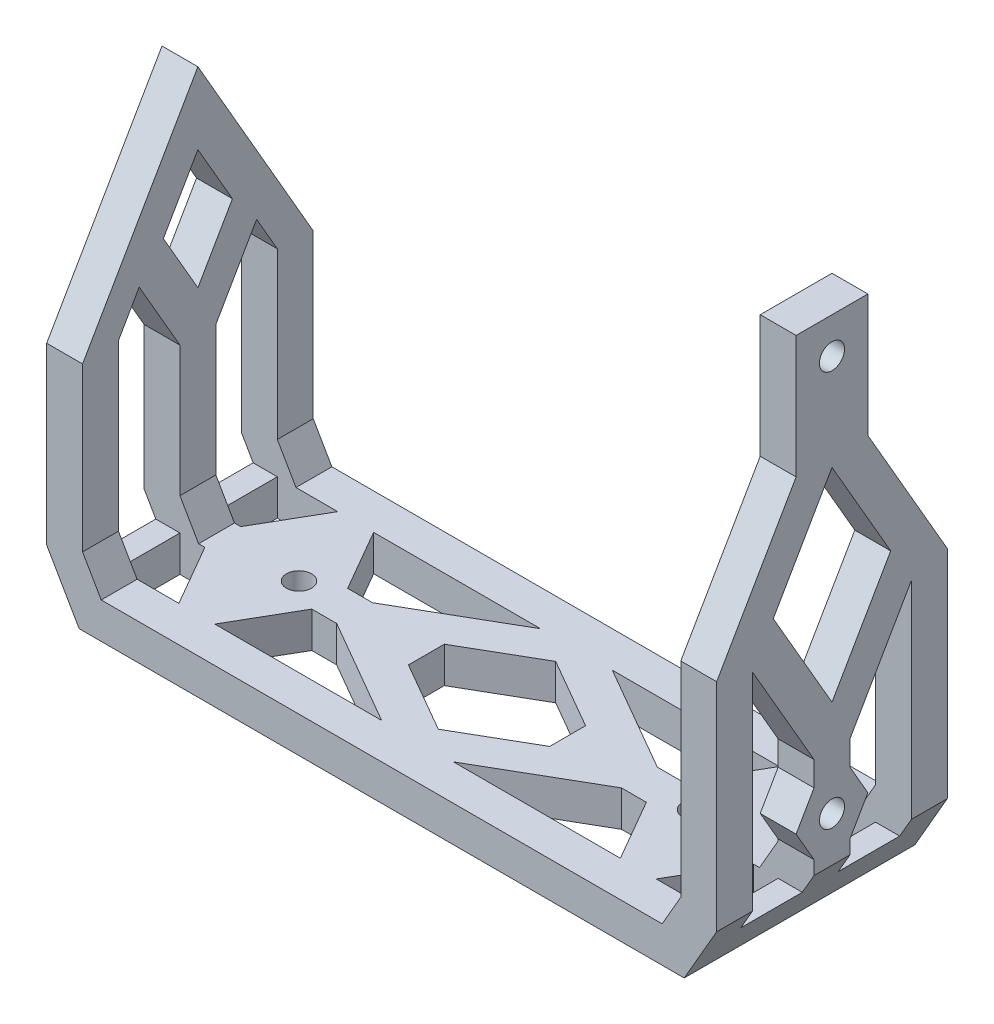
SolidWorks part; units mm, degrees
material "ABS"
ref_plane "Front Plane" through (0, 0, 0) normal (0, 0, 1) x (1, 0, 0)
ref_plane "Top Plane" through (0, 0, 0) normal (0, 1, 0) x (1, 0, 0)
ref_plane "Right Plane" through (0, 0, 0) normal (1, 0, 0) x (0, 0, -1)
sketch "Sketch1" plane through (0, 0, 0) normal (0, 1, 0) x (1, 0, 0)
  line L0 (-16.55, 0) -> (16.55, 0) construction
  line L1 (-5.9019, 1.5) -> (0, 4.9075)
  line L2 (-28, -1.5) -> (28, -1.5) construction
  line L3 (-28, -1.5) -> (-28, 1.5)
  line L4 (-28, 1.5) -> (28, 1.5) construction
  line L5 (28, -1.5) -> (28, 1.5)
  line L6 (-28, -1.5) -> (28, 1.5) construction
  line L7 (-28, 1.5) -> (28, -1.5) construction
  line L8 (0, 4.9075) -> (5.9019, 1.5)
  line L9 (-11.9019, 1.5) -> (-3, 6.6395)
  line L10 (11.9019, 1.5) -> (3, 6.6395)
  line L11 (0, 4.9075) -> (0, 6.6395) construction
  line L12 (-3, 6.6395) -> (3, 6.6395) construction
  line L13 (-28, 9.6395) -> (-28, 6.6395)
  line L14 (-28, 9.6395) -> (28, 9.6395)
  line L15 (-28, 6.6395) -> (28, 6.6395) construction
  line L16 (28, 9.6395) -> (28, 6.6395)
  line L17 (-28, 9.6395) -> (28, 6.6395) construction
  line L18 (-28, 6.6395) -> (28, 9.6395) construction
  line L19 (-11.9019, 1.5) -> (-5.9019, 1.5) construction
  line L20 (-5.9019, -1.5) -> (0, -4.9075)
  line L21 (5.9019, -1.5) -> (0, -4.9075)
  line L22 (-11.9019, -1.5) -> (-3, -6.6395)
  line L23 (11.9019, -1.5) -> (3, -6.6395)
  line L24 (0, -4.9075) -> (0, -6.6395) construction
  line L25 (-3, -6.6395) -> (3, -6.6395) construction
  line L26 (-28, -9.6395) -> (-28, -6.6395)
  line L27 (-28, -9.6395) -> (28, -9.6395)
  line L28 (-28, -6.6395) -> (28, -6.6395) construction
  line L29 (28, -9.6395) -> (28, -6.6395)
  line L30 (-28, -9.6395) -> (28, -6.6395) construction
  line L31 (-28, -6.6395) -> (28, -9.6395) construction
  line L32 (-28, 1.5) -> (-11.9019, 1.5)
  line L33 (-11.9019, -1.5) -> (-28, -1.5)
  line L34 (-28, 6.6395) -> (-3, 6.6395)
  line L35 (-3, -6.6395) -> (-28, -6.6395)
  line L36 (3, -6.6395) -> (28, -6.6395)
  line L37 (11.9019, -1.5) -> (28, -1.5)
  line L38 (3, 6.6395) -> (28, 6.6395)
  line L39 (-5.9019, 1.5) -> (-5.9019, -1.5)
  line L40 (5.9019, 1.5) -> (5.9019, -1.5)
  line L41 (11.9019, 1.5) -> (28, 1.5)
  circle A0 centre (0, 0) radius 4.25 construction
  circle A2 centre (-16.55, 0) radius 1.05
  circle A3 centre (16.55, 0) radius 1.05
  point P8 (0, 0)
  point P18 (0, 8.1395)
  point P23 (0, 6.6395)
  point P33 (0, -8.1395)
  point P37 (0, -6.6395)
  dimension "D1" = 8.5
  dimension "D4" = 2.1
  dimension "D3" = 33.1
  dimension "D5" = 3
  dimension "D6" = 56
  dimension "D7" = 30
  dimension "D8" = 3
extrude "Boss-Extrude1" add sketch "Sketch1" against normal blind 3
sketch "Sketch4" plane through (0, 0, 0) normal (0, 1, 0) x (1, 0, 0)
  line L0 (-28, 1.5) -> (-11.9019, 1.5) construction
  line L1 (-28, 6.6395) -> (-25, 6.6395)
  line L2 (-28, 6.6395) -> (-28, 1.5)
  line L3 (-28, 1.5) -> (-25, 1.5)
  line L4 (-25, 6.6395) -> (-25, 1.5)
  line L10 (-13.9837, 1.5) -> (-16.951, 6.6395)
  line L15 (-28, 6.6395) -> (-3, 6.6395) construction
  line L16 (-19.951, 6.6395) -> (-22.9183, 1.5)
  line L17 (-19.951, 6.6395) -> (-16.951, 6.6395)
  line L18 (-22.9183, 1.5) -> (-25, 1.5) construction
  line L19 (-13.9837, 1.5) -> (-11.9019, 1.5) construction
  line L20 (-22.9183, 1.5) -> (-13.9837, 1.5)
  dimension "D1" = 3
  dimension "D2" = 60
  dimension "D3" = 60
extrude "Boss-Extrude5" add sketch "Sketch4" against normal blind 3
mirror "Mirror2" about plane through (0, 0, 0) normal (0, 0, 1) of "Boss-Extrude5"
mirror "Mirror3" about plane through (0, 0, 0) normal (1, 0, 0) of "Mirror2", "Boss-Extrude5"
sketch "Sketch5" plane through (28, 0, 0) normal (1, 0, 0) x (0, 0, -1)
  line L0 (0, 0) -> (0, -3) construction
  line L1 (9.6395, -3) -> (-9.6395, -3) construction
  line L2 (0, 0) -> (0, 22) construction
  line L3 (0, 38.55) -> (0, 5.45) construction
  line L4 (-9.6395, 0) -> (9.6395, 0) construction
  line L5 (-1.5, 0) -> (1.5, 0)
  line L6 (-1.5, 0) -> (-1.5, 41.55) construction
  line L7 (-1.5, 41.55) -> (1.5, 41.55) construction
  line L8 (1.5, 0) -> (1.5, 41.55) construction
  line L9 (-1.5, 27.9019) -> (-4.9075, 22)
  line L10 (-4.9075, 22) -> (-1.5, 16.0981)
  line L11 (-1.5, 10.0981) -> (-6.6395, 19)
  line L12 (-4.9075, 22) -> (-6.6395, 22) construction
  line L13 (-6.6395, 25) -> (-6.6395, 19) construction
  line L14 (-6.6395, 25) -> (-1.5, 33.9019) construction
  line L15 (-1.5, 10.0981) -> (-1.5, 16.0981) construction
  line L20 (-6.6395, 25) -> (-9.6395, 25) construction
  line L21 (-6.6395, 25) -> (-6.6395, 0) construction
  line L22 (-6.6395, 0) -> (-9.6395, 0)
  line L23 (-9.6395, 25) -> (-9.6395, 0) construction
  line L24 (-6.6395, 19) -> (-6.6395, 0)
  line L25 (1.5, 27.9019) -> (4.9075, 22)
  line L26 (4.9075, 22) -> (1.5, 16.0981)
  line L27 (1.5, 10.0981) -> (6.6395, 19)
  line L28 (1.5, 16.0981) -> (1.5, 10.0981) construction
  line L29 (6.6395, 19) -> (6.6395, 25) construction
  line L30 (6.6395, 25) -> (1.5, 33.9019) construction
  line L31 (6.6395, 25) -> (9.6395, 25) construction
  line L32 (9.6395, 25) -> (9.6395, 0) construction
  line L33 (9.6395, 0) -> (6.6395, 0)
  line L34 (6.6395, 0) -> (6.6395, 19)
  line L35 (-1.5, 10.0981) -> (-1.5, 0) construction
  line L36 (1.5, 10.0981) -> (1.5, 0) construction
  line L37 (-1.5, 16.0981) -> (0, 13.5)
  line L38 (1.5, 16.0981) -> (0, 13.5)
  line L39 (-1.5, 27.9019) -> (0, 30.5)
  line L40 (0, 30.5) -> (1.5, 27.9019)
  line L41 (-1.5, 33.9019) -> (-1.5, 41.55) construction
  line L42 (1.5, 33.9019) -> (1.5, 41.55) construction
  line L43 (-6.6395, 25) -> (-9.6395, 19.8038)
  line L44 (-9.6395, 19.8038) -> (-9.6395, 0)
  line L45 (6.6395, 25) -> (9.6395, 19.8038)
  line L46 (9.6395, 19.8038) -> (9.6395, 0)
  line L47 (3, 41.55) -> (-3, 41.55)
  line L48 (-3, 41.55) -> (-3, 31.3038)
  line L49 (3, 41.55) -> (3, 31.3038)
  line L50 (6.6395, 25) -> (3, 31.3038)
  line L51 (-6.6395, 25) -> (-3, 31.3038)
  line L52 (-1.5, 2.8519) -> (-3, 5.45)
  line L53 (-3, 5.45) -> (-1.5, 8.0481)
  line L54 (1.5, 2.8519) -> (3, 5.45)
  line L55 (3, 5.45) -> (1.5, 8.0481)
  line L56 (-3, 5.45) -> (3, 5.45) construction
  line L57 (-1.5, 8.0481) -> (-1.5, 10.0981)
  line L58 (-1.5, 2.8519) -> (-1.5, 0)
  line L59 (1.5, 10.0981) -> (1.5, 8.0481)
  line L60 (1.5, 2.8519) -> (1.5, 0)
  circle A0 centre (0, 22) radius 4.25 construction
  circle A1 centre (0, 38.55) radius 1.05
  circle A2 centre (0, 5.45) radius 1.05
  point P9 (0, 22)
  point P27 (-6.6395, 22)
  point P47 (0, 41.55)
  point P58 (0, 5.45)
  dimension "D5" = 3
  dimension "D7" = 30
  dimension "D8" = 3
  dimension "D2" = 2.1
  dimension "D3" = 8.5
  dimension "D1" = 22
  dimension "D4" = 33.1
  dimension "D6" = 3
  dimension "D9" = 6
  dimension "D10" = 6
  dimension "D11" = 30
extrude "Boss-Extrude6" add sketch "Sketch5" against normal blind 3
chamfer "Chamfer2" distance 10 angle 30 9 edges at (22.4755, 0, 6.6395) (23.9591, 0, 1.5) (21.4346, 0, 4.0698) (23.9591, 0, -1.5) (22.4755, 0, -6.6395) (21.4346, 0, -4.0698) (25, 0, 8.1395) (25, 0, -8.1395) (25, 0, 0)
sketch "Sketch8" plane through (-28, 0, 0) normal (-1, 0, 0) x (0, 0, 1)
  line L0 (0, 0) -> (0, 22) construction
  line L1 (0, 17) -> (2.8868, 22)
  line L2 (2.8868, 22) -> (0, 27)
  line L3 (0, 27) -> (-2.8868, 22)
  line L4 (-2.8868, 22) -> (0, 17)
  line L5 (0, 33) -> (-6.3509, 22)
  line L6 (-6.3509, 22) -> (0, 11) construction
  line L7 (0, 11) -> (6.3509, 22) construction
  line L8 (6.3509, 22) -> (0, 33)
  line L9 (-9.6395, 0) -> (-9.6395, 16.3038)
  line L10 (-9.6395, 10) -> (-9.6395, 19.8038) construction
  line L11 (-9.6395, 16.3038) -> (-6.3509, 22)
  line L12 (0, 5) -> (-6.6395, 16.5) construction
  line L13 (0, 5) -> (6.6395, 16.5) construction
  line L14 (-6.6395, 16.5) -> (-6.6395, 0)
  line L15 (-6.6395, 19) -> (-6.6395, 10) construction
  line L16 (9.6395, 0) -> (-9.6395, 0) construction
  line L17 (-6.6395, 0) -> (-9.6395, 0)
  line L18 (6.6395, 16.5) -> (6.6395, 0)
  line L19 (6.6395, 10) -> (6.6395, 19) construction
  line L20 (6.6395, 0) -> (9.6395, 0)
  line L21 (9.6395, 0) -> (9.6395, 16.3038)
  line L22 (9.6395, 19.8038) -> (9.6395, 10) construction
  line L23 (9.6395, 16.3038) -> (6.3509, 22)
  line L24 (6.6395, 16.5) -> (4.9075, 19.5)
  line L25 (-6.6395, 16.5) -> (-4.9075, 19.5)
  line L26 (1.5, 13.5981) -> (1.5, 0)
  line L27 (9.6395, 0) -> (-9.6395, 0) construction
  line L28 (-1.5, 13.5981) -> (-1.5, 0)
  line L29 (-1.5, 0) -> (1.5, 0)
  line L30 (-4.9075, 19.5) -> (-1.5, 13.5981)
  line L31 (1.5, 13.5981) -> (4.9075, 19.5)
  line L32 (-6.6395, 10.5) -> (-1.5, 1.5981) construction
  line L33 (1.5, 1.5981) -> (6.6395, 10.5) construction
  line L36 (-1.5, 7.5981) -> (-6.6395, 16.5) construction
  line L38 (6.6395, 16.5) -> (1.5, 7.5981) construction
  circle A0 centre (0, 22) radius 2.5 construction
  point P47 (-6.6395, 10.5)
  dimension "D5" = 3
  dimension "D8" = 3
  dimension "D1" = 22
  dimension "D6" = 3
  dimension "D2" = 5
  dimension "D3" = 30
  dimension "D7" = 3
  dimension "D4" = 3
extrude "Boss-Extrude8" add sketch "Sketch8" against normal blind 3
sketch "Sketch11" plane through (0, 0, -9.6395) normal (0, 0, -1) x (-1, 0, 0)
  line L0 (-19.2265, 0) -> (-25, 0)
  line L1 (-25, 0) -> (-25, 10)
  line L2 (-25, 10) -> (-19.2265, 0)
extrude "Cut-Extrude3" cut sketch "Sketch11" against normal up to surface (19.2791 mm away) up to face at (2.1363, 8.4684, 9.6395)
sketch "Sketch12" plane through (0, 0, -9.6395) normal (0, 0, -1) x (-1, 0, 0)
  line L0 (-18.0718, 0) -> (-25, 12)
  line L1 (25, 0) -> (-25, 0) construction
  line L2 (-25, 0) -> (-25, 19.8038) construction
  line L3 (-25, 12) -> (-25, 0) construction
  line L4 (-25, 0) -> (-18.0718, 0) construction
  line L5 (-25, 6) -> (-21.5359, 0)
  line L6 (-25, 12) -> (-25, 6)
  line L7 (-21.5359, 0) -> (-18.0718, 0)
  dimension "D1" = 60
  dimension "D2" = 3
  dimension "D3" = 3
extrude "Boss-Extrude10" [suppressed] add sketch "Sketch12" against normal blind 3
mirror "Mirror9" [suppressed] about plane through (0, 0, 0) normal (0, 0, 1)
mirror "Mirror10" [suppressed] about plane through (0, 0, 0) normal (1, 0, 0)
chamfer "Chamfer4" distance 2.7 angle 30 6 edges at (-25, 0, -8.1395) (-25, 0, 0) (-25, 0, 8.1395) (25, 0, 8.1395) (25, 0, 0) (25, 0, -8.1395)
chamfer "Chamfer5" distance 4.7 angle 30 2 edges at (28, -3, 0) (-28, -3, 0)
equation "\"thiccness\" = 3mm"
equation "\"reg-tolerance\"= .2mm"
equation "\"tight-tolerance\"= .15mm"
equation "\"loose-tolerance\"= .3mm"
equation "\"D4@Sketch1\"=\"loose-tolerance\"*2+1.5"
equation "\"D5@Sketch1\"=\"thiccness\""
equation "\"D6@Sketch1\"=\"thiccness\"*2+50"
equation "\"D1@Boss-Extrude1\"= \"thiccness\""
equation "\"D7@Sketch1\"=30"
equation "\"D8@Sketch1\"=\"thiccness\""
equation "\"D1@Sketch4\"= \"thiccness\""
equation "\"D1@Boss-Extrude5\"=\"thiccness\""
equation "\"D2@Sketch5\"=1.5+\"loose-tolerance\"*2"
equation "\"D5@Sketch5\"=\"thiccness\""
equation "\"D6@Sketch5\"=\"thiccness\""
equation "\"D8@Sketch5\"=\"thiccness\""
equation "\"D1@Boss-Extrude6\"=\"thiccness\""
equation "\"tilt-axis-height\" = 22mm"
equation "\"D1@Sketch5\"=\"tilt-axis-height\""
equation "\"D1@Sketch8\"=\"tilt-axis-height\""
equation "\"D4@Sketch8\"=\"thiccness\""
equation "\"D5@Sketch8\"=\"thiccness\""
equation "\"D6@Sketch8\"=\"thiccness\""
equation "\"D7@Sketch8\"=\"thiccness\""
equation "\"D8@Sketch8\"=\"thiccness\""
equation "\"D1@Boss-Extrude8\"=\"thiccness\""
equation "\"D3@Sketch12\"=\"thiccness\""
equation "\"D1@Boss-Extrude10\"=\"thiccness\""
equation "\"D9@Sketch5\"=\"D6@Sketch5\"+3"
equation "\"D10@Sketch5\"=\"D9@Sketch5\""
